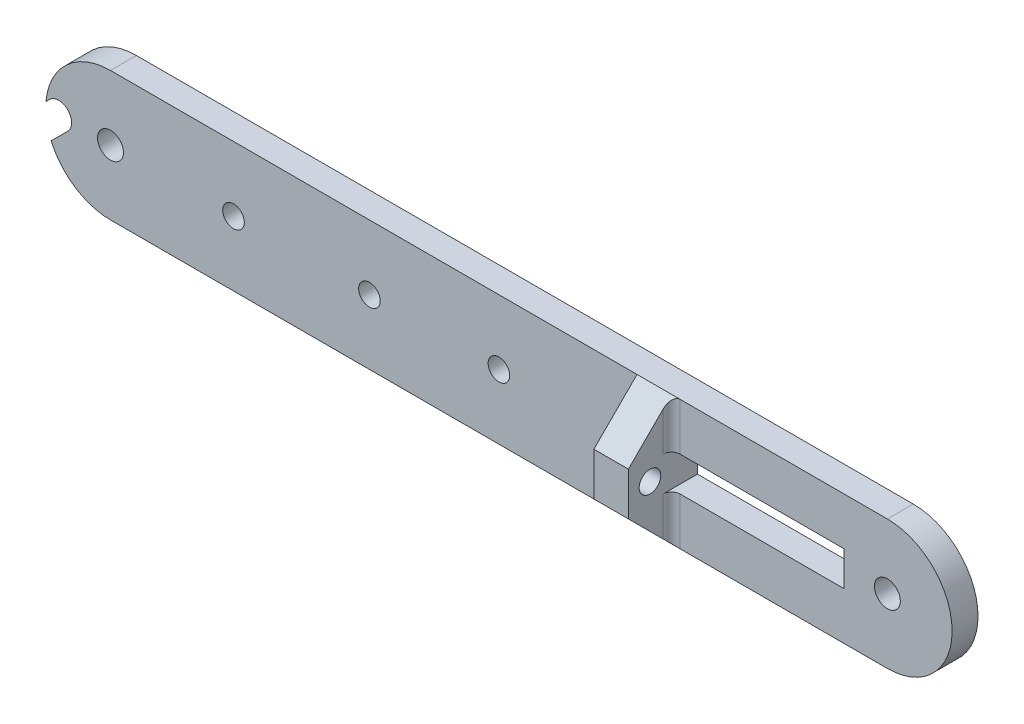
SolidWorks part; units mm, degrees
ref_plane "Plan de face" through (0, 0, 0) normal (0, 0, 1) x (1, 0, 0)
ref_plane "Plan de dessus" through (0, 0, 0) normal (0, 1, 0) x (1, 0, 0)
ref_plane "Plan de droite" through (0, 0, 0) normal (1, 0, 0) x (0, 0, -1)
sketch "Esquisse1" plane through (0, 0, 0) normal (0, 0, 1) x (1, 0, 0)
  line L0 (-74.3787, 0) -> (69.7437, 0) construction
  line L1 (0, 0) -> (0, 19.0596) construction
  line L2 (90, -15) -> (-90, -15)
  line L3 (90, 15) -> (-90, 15)
  line L5 (40, -4) -> (80, -4)
  line L6 (40, -4) -> (40, 4)
  line L7 (40, 4) -> (80, 4)
  line L8 (80, -4) -> (80, 4)
  line L9 (40, -4) -> (80, 4) construction
  line L10 (40, 4) -> (80, -4) construction
  arc A0 (90, -15) -> (90, 15) centre (90, 0) ccw
  circle A1 centre (90, 0) radius 3
  circle A2 centre (-90, 0) radius 3
  arc A3 (-90, -15) -> (-90, 15) centre (-90, 0) cw
  circle A4 centre (0, 0) radius 2.5
  circle A5 centre (-61.5, 0) radius 2.5
  circle A6 centre (-30, 0) radius 2.5
  point P4 (60, 0)
  point P17 (0, -15)
  point P20 (0, 15)
  dimension "D1" = 30
  dimension "D3" = 6
  dimension "D7" = 5
  dimension "D8" = 5
  dimension "D9" = 5
  dimension "D10" = 61.5
  dimension "D2" = 90
  dimension "D4" = 8
  dimension "D5" = 40
  dimension "D6" = 60
  dimension "D11" = 30
extrude "Boss.-Extru.1" add sketch "Esquisse1" along normal blind 6
sketch "Esquisse2" plane through (40, 0, 0) normal (1, 0, 0) x (0, 0, -1)
  line L0 (0, -4) -> (-6, 4) construction
  line L1 (-6, 4) -> (-6, 0) construction
  line L2 (-6, 4) -> (-6, -4) construction
  line L3 (-6, 0) -> (-15.5036, 0) construction
  line L4 (-6, 15) -> (-6, -15) construction
  line L6 (-16, 5) -> (-16, -5)
  line L8 (-6, 5) -> (-6, -5)
  line L9 (-16, 5) -> (-6, -5) construction
  line L10 (-16, -5) -> (-6, 5) construction
  line L11 (-6, -15) -> (-16, -5)
  line L12 (-6, -15) -> (-6, -5)
  line L13 (-6, 5) -> (-6, 15)
  line L14 (-6, 15) -> (-16, 5)
  circle A0 centre (-11, 0) radius 2.5
  point P7 (-11, 0)
  dimension "D3" = 5
  dimension "D1" = 10
  dimension "D2" = 10
extrude "Boss.-Extru.2" add sketch "Esquisse2" against normal blind 8
fillet "Congé2" radius 2 2 edges
sketch "Esquisse3" plane through (32, 0, 0) normal (-1, 0, 0) x (0, 0, 1)
  line L0 (11, 0) -> (11, 4) construction
  line L1 (11, 0) -> (14.4641, 2) construction
  line L2 (11, 0) -> (14.4641, -2) construction
  line L3 (11, 4) -> (14.4641, 2)
  line L4 (14.4641, 2) -> (14.4641, -2)
  line L5 (14.4641, -2) -> (11, -4)
  line L6 (7.5359, 2) -> (7.5359, -2)
  line L7 (11, 4) -> (7.5359, 2)
  line L8 (7.5359, -2) -> (11, -4)
  dimension "D2" = 60
  dimension "D3" = 60
extrude "Enlèv. mat.-Extru.1" cut sketch "Esquisse3" against normal blind 4
sketch "Esquisse4" plane through (0, 0, 6) normal (0, 0, 1) x (1, 0, 0)
  line L0 (-90, 0) -> (-105, 0) construction
  line L1 (-105, 0) -> (-102, 0) construction
  line L2 (-102, 0) -> (-99.8787, -2.1213) construction
  line L3 (-99.8787, -2.1213) -> (-104.1213, 2.1213)
  line L4 (-99.8787, -2.1213) -> (-104.1213, 2.1213)
  line L5 (-99.8787, -2.1213) -> (-104.2614, -6.504)
  line L6 (-104.1213, 2.1213) -> (-108.504, -2.2614)
  line L7 (-104.2614, -6.504) -> (-108.504, -2.2614)
  arc A0 (-90, 15) -> (-90, -15) centre (-90, 0) ccw construction
  circle A1 centre (-102, 0) radius 3
  arc M9 (-90, 15) -> (-90, -15) centre (-90, 0) ccw
  dimension "D1" = 3
  dimension "D2" = 135
extrude "Enlèv. mat.-Extru.4" cut sketch "Esquisse4" against normal blind 10 contours L3 A1 | A1 L6 M9 | A1 L5 M9 | L3 A1 region at (-102.9003, -0.9003, 6) region at (-101.0997, 0.9003, 6) region at (-103.2777, -3.6386, 6) region at (-104.7977, 1.1965, 6)
